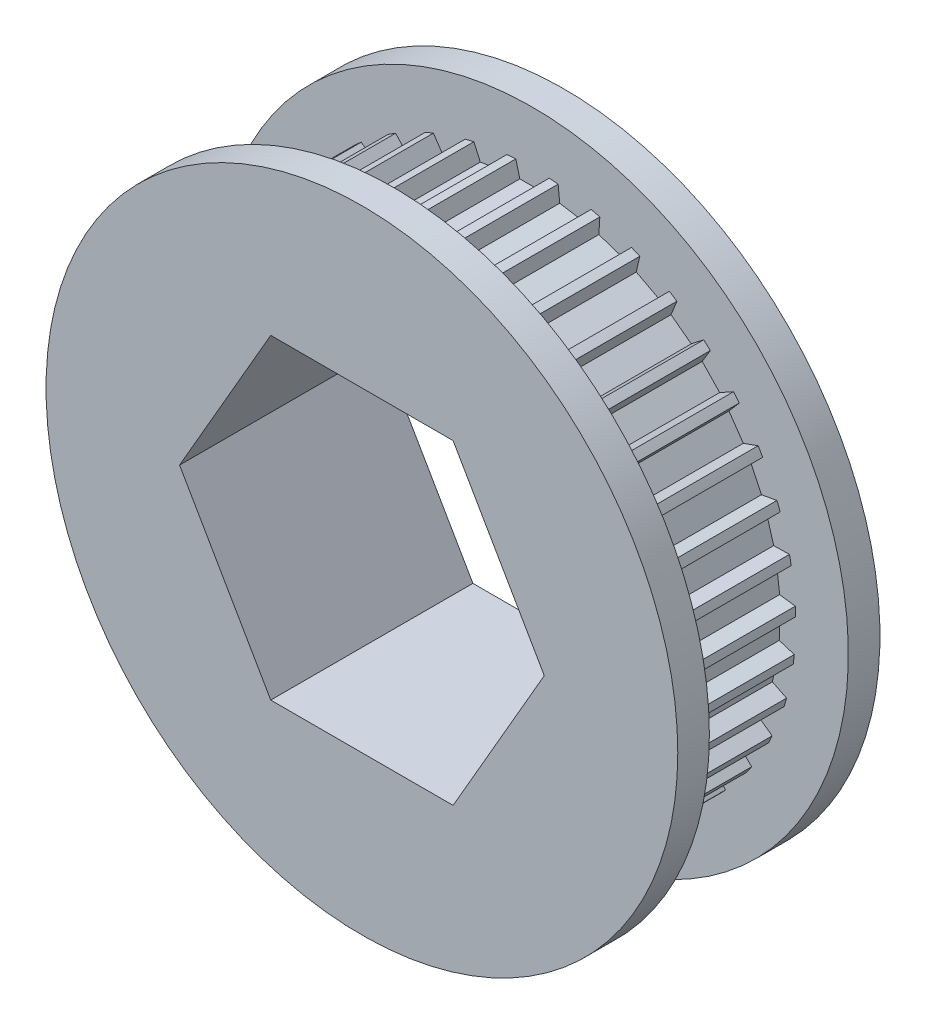
SolidWorks part; units mm, degrees
ref_plane "Front Plane" through (0, 0, 0) normal (0, 0, 1) x (1, 0, 0)
ref_plane "Top Plane" through (0, 0, 0) normal (0, 1, 0) x (1, 0, 0)
ref_plane "Right Plane" through (0, 0, 0) normal (1, 0, 0) x (0, 0, -1)
sketch "Sketch1" plane through (0, 0, 0) normal (0, 0, 1) x (1, 0, 0)
  circle A0 centre (0, 0) radius 12.5
  dimension "D1" = 25
extrude "Boss-Extrude1" add sketch "Sketch1" along normal mid plane 6.6
sketch "Sketch3" plane through (0, 0, 3.3) normal (0, 0, 1) x (1, 0, 0)
  circle A0 centre (0, 0) radius 15
  dimension "D1" = 30
sketch "Sketch2" plane through (0, 0, -3.3) normal (0, 0, -1) x (-1, 0, 0)
  circle A0 centre (0, 0) radius 15
  dimension "D1" = 30
sketch "Sketch4" plane through (0, 0, 3.3) normal (0, 0, 1) x (1, 0, 0)
  line L0 (-0.6, 11.75) -> (0.6, 11.75)
  line L1 (0.6, 11.75) -> (0.8, 12.5)
  line L2 (0.8, 12.5) -> (-0.8, 12.5)
  line L3 (-0.8, 12.5) -> (-0.6, 11.75)
  circle A0 centre (0, 0) radius 12.5 construction
  point P4 (-1.967, 18.9038)
  point P5 (-2.8978, 18.7672)
  point P6 (-1.3713, 18.4756)
  point P7 (-1.4024, 17.6875)
  point P10 (0, 11.75)
  dimension "D1" = 1.2
  dimension "D2" = 1.6
  dimension "D3" = 0.75
extrude "Cut-Extrude1" cut sketch "Sketch4" against normal up to surface (6.6 mm away) and the other way through all up to face at (12.5, 0, -3.3)
pattern_circular "CirPattern2" count 39 over 360 about axis through (0, 0, 3.3) along (0, 0, 1) of "Cut-Extrude1"
extrude "Boss-Extrude3" add sketch "Sketch2" along normal blind 1.5
extrude "Boss-Extrude4" add sketch "Sketch3" along normal blind 1.5 contours A0
sketch "Sketch5" plane through (0, 0, 4.8) normal (0, 0, 1) x (1, 0, 0)
  line L1 (8.6603, 0) -> (4.3301, 7.5)
  line L2 (4.3301, 7.5) -> (-4.3301, 7.5)
  line L3 (-4.3301, 7.5) -> (-8.6603, 0)
  line L4 (-8.6603, 0) -> (-4.3301, -7.5)
  line L5 (-4.3301, -7.5) -> (4.3301, -7.5)
  line L6 (4.3301, -7.5) -> (8.6603, 0)
  circle A0 centre (0, 0) radius 7.5 construction
  point P1 (0, -7.5)
  dimension "D1" = 15
extrude "Cut-Extrude2" cut sketch "Sketch5" against normal through all both and the other way through all
